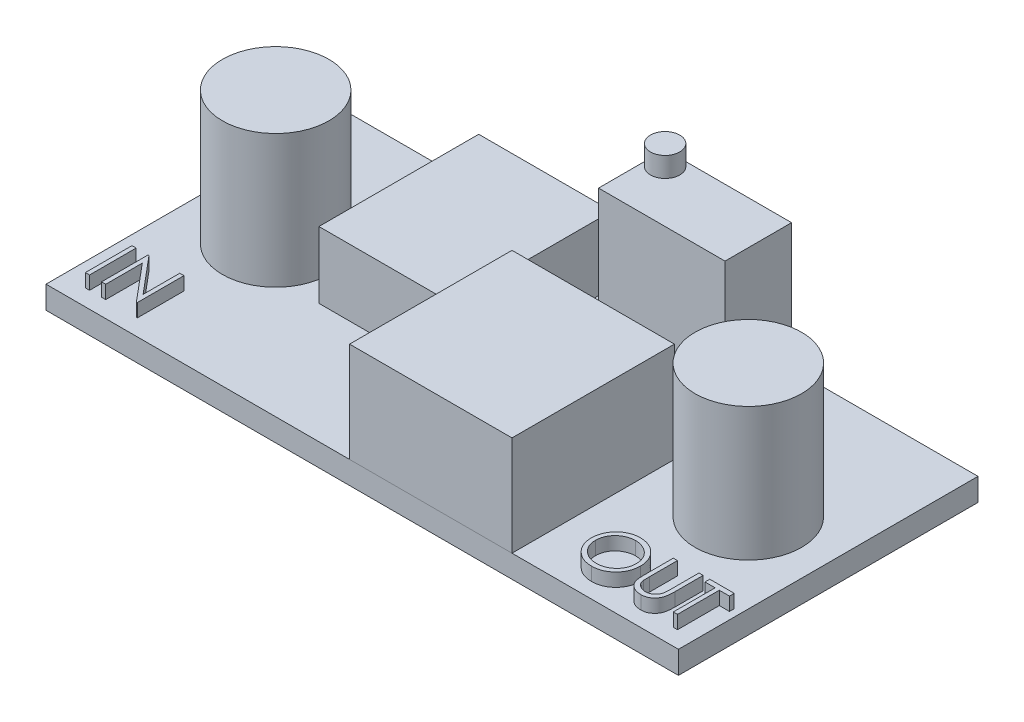
SolidWorks part; units mm, degrees
ref_plane "Front Plane" through (0, 0, 0) normal (0, 0, 1) x (1, 0, 0)
ref_plane "Top Plane" through (0, 0, 0) normal (0, 1, 0) x (1, 0, 0)
ref_plane "Right Plane" through (0, 0, 0) normal (1, 0, 0) x (0, 0, -1)
sketch "Sketch1" plane through (0, 0, 0) normal (0, 1, 0) x (1, 0, 0)
  line L1 (-23.75, -11.25) -> (23.75, -11.25)
  line L2 (-23.75, -11.25) -> (-23.75, 11.25)
  line L3 (-23.75, 11.25) -> (23.75, 11.25)
  line L4 (23.75, -11.25) -> (23.75, 11.25)
  line L5 (-23.75, -11.25) -> (23.75, 11.25) construction
  line L6 (-23.75, 11.25) -> (23.75, -11.25) construction
  point P0 (0, 0)
  dimension "D1" = 22.5
  dimension "D2" = 47.5
extrude "Boss-Extrude1" add sketch "Sketch1" along normal blind 1.7 contours L3 L4 L1 L2
sketch "Sketch2" plane through (0, 1.7, 0) normal (0, 1, 0) x (1, 0, 0)
  line L0 (23.75, -11.25) -> (23.75, 11.25) construction
  line L1 (-23.75, -11.25) -> (-23.75, 11.25) construction
  circle A0 centre (17.75, 0) radius 4
  circle A1 centre (-17.75, 0) radius 4
  dimension "D3" = 8
  dimension "D1" = 6
  dimension "D2" = 6
extrude "Boss-Extrude2" add sketch "Sketch2" along normal blind 10 separate body
sketch "Sketch3" plane through (0, 1.7, 0) normal (0, 1, 0) x (1, 0, 0)
  line L0 (23.75, -11.25) -> (23.75, 11.25) construction
  line L1 (10.75, 10.25) -> (1.25, 10.25)
  line L2 (10.75, 10.25) -> (10.75, 5.25)
  line L3 (10.75, 5.25) -> (1.25, 5.25)
  line L4 (1.25, 10.25) -> (1.25, 5.25)
  line L5 (11.25, 0.95) -> (-0.95, 0.95)
  line L6 (11.25, 0.95) -> (11.25, -11.25)
  line L7 (11.25, -11.25) -> (-0.95, -11.25)
  line L8 (-0.95, 0.95) -> (-0.95, -11.25)
  line L9 (-2.25, 9.75) -> (-12.25, 9.75)
  line L10 (-2.25, 9.75) -> (-2.25, -2.25)
  line L11 (-2.25, -2.25) -> (-12.25, -2.25)
  line L12 (-12.25, 9.75) -> (-12.25, -2.25)
  line L13 (-23.75, -11.25) -> (23.75, -11.25) construction
  line L14 (-23.75, 11.25) -> (23.75, 11.25) construction
  line L15 (-23.75, -11.25) -> (-23.75, 11.25) construction
  line M12 (-23.75, -11.25) -> (23.75, -11.25)
  dimension "D1" = 12.2
  dimension "D2" = 12.5
  dimension "D3" = 0
  dimension "D4" = 9.5
  dimension "D5" = 5
  dimension "D6" = 13
  dimension "D7" = 1
  dimension "D8" = 10
  dimension "D9" = 12
  dimension "D10" = 1.5
  dimension "D11" = 11.5
extrude "Boss-Extrude3" add sketch "Sketch3" along normal blind 7.5 separate body contours L5 L8 L6 M12 region at (5.15, 1.7, 5.15)
extrude "Boss-Extrude4" add sketch "Sketch3<3>" along normal blind 10.5 separate body contours L1 L4 L3 L2
sketch "Sketch3<3>" plane through (0, 1.7, 0) normal (0, 1, 0) x (1, 0, 0) same geometry as "Sketch3"
extrude "Boss-Extrude5" add sketch "Sketch3<4>" along normal blind 5 separate body contours L9 L12 L11 L10
sketch "Sketch3<4>" plane through (0, 1.7, 0) normal (0, 1, 0) x (1, 0, 0) same geometry as "Sketch3"
sketch "Sketch4" plane through (0, 1.7, 0) normal (0, 1, 0) x (1, 0, 0)
  text T0 "IN"
  text T1 "OUT"
extrude "Boss-Extrude6" add sketch "Sketch4" along normal blind 1
sketch "Sketch5" plane through (0, 12.2, 0) normal (0, 1, 0) x (1, 0, 0)
  line L0 (1.25, 10.25) -> (1.25, 5.25) construction
  line L1 (10.75, 10.25) -> (1.25, 10.25) construction
  circle A0 centre (2.35, 9.15) radius 1.1
  dimension "D1" = 2.2
extrude "Boss-Extrude7" add sketch "Sketch5" along normal blind 1.5
ref_plane "Plane1" through (0, 0, 0) normal (0, 0, 1) x (1, 0, 0)
other "Freeze***"
